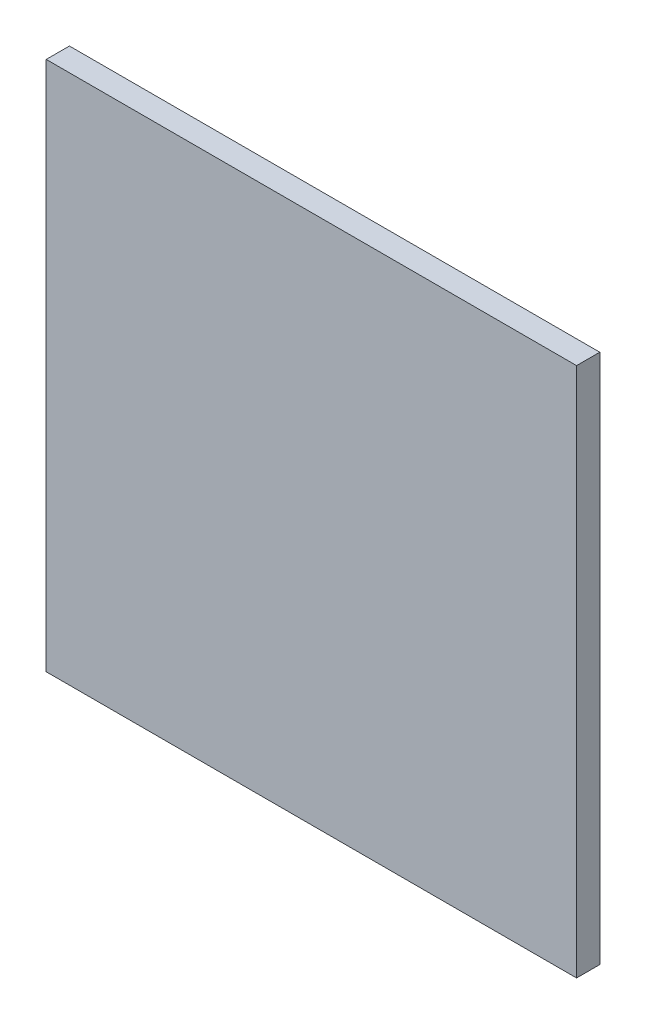
SolidWorks part; units mm, degrees
ref_plane "Přední rovina" through (0, 0, 0) normal (0, 0, 1) x (1, 0, 0)
ref_plane "Horní rovina" through (0, 0, 0) normal (0, 1, 0) x (1, 0, 0)
ref_plane "Pravá rovina" through (0, 0, 0) normal (1, 0, 0) x (0, 0, -1)
sketch "Skica1" plane through (0, 0, 0) normal (0, 0, 1) x (1, 0, 0)
  line L0 (0, 87.2534) -> (0, -76) construction
  line L1 (-79.5197, 0) -> (109.1421, 0) construction
  line L2 (11, 51) -> (-11, 51)
  line L3 (11, 27) -> (11, 51)
  line L4 (27, 27) -> (11, 27)
  line L5 (27, 11) -> (27, 27)
  line L6 (51, 11) -> (27, 11)
  line L7 (51, 11) -> (51, -11)
  line L8 (51, -11) -> (27, -11)
  line L9 (27, -11) -> (27, -27)
  line L10 (27, -27) -> (11, -27)
  line L11 (11, -27) -> (11, -51)
  line L12 (11, -51) -> (-11, -51)
  line L13 (-11, -27) -> (-11, -51)
  line L14 (-27, -27) -> (-11, -27)
  line L15 (-27, -11) -> (-27, -27)
  line L16 (-51, -11) -> (-27, -11)
  line L17 (-51, 11) -> (-51, -11)
  line L18 (-51, 11) -> (-27, 11)
  line L19 (-27, 11) -> (-27, 27)
  line L20 (-27, 27) -> (-11, 27)
  line L21 (-11, 27) -> (-11, 51)
  line L23 (-80, 80) -> (80, 80)
  line L24 (-80, 80) -> (-80, -80)
  line L25 (-80, -80) -> (80, -80)
  line L26 (80, 80) -> (80, -80)
  circle A0 centre (0, 0) radius 76
  point P17 (51, 0)
  point P21 (0, -51)
  point P30 (0, 51)
  dimension "D1" = 152
  dimension "D2" = 25
  dimension "D3" = 11
  dimension "D4" = 24
  dimension "D5" = 16
  dimension "D6" = 11
  dimension "D7" = 16
  dimension "D8" = 24
  dimension "D9" = 160
  dimension "D10" = 80
  dimension "D11" = 80
  dimension "D12" = 160
extrude "Přidat vysunutím1" add sketch "Skica1" along normal blind 7 contours L23 L26 L25 L24
extrude "Odebrat vysunutím1" cut sketch "Skica1<5>" along normal blind 1 contours L21 L20 L19 L18 L17 L16 L15 L14 L13 L12 L11 L10 L9 L8 L7 L6 L5 L4 L3 L2 region at (0, 0, 0)
sketch "Skica1<5>" plane through (0, 0, 0) normal (0, 0, 1) x (1, 0, 0) same geometry as "Skica1"
extrude "Odebrat vysunutím3" cut sketch "Skica1<6>" along normal blind 3 contours A0 L20 L21 L2 L3 L4 L5 L6 L7 L8 L9 L10 L11 L12 L13 L14 L15 L16 L17 L18 L19 region at (-73.8504, 0, 0)
sketch "Skica1<6>" plane through (0, 0, 0) normal (0, 0, 1) x (1, 0, 0) same geometry as "Skica1"
